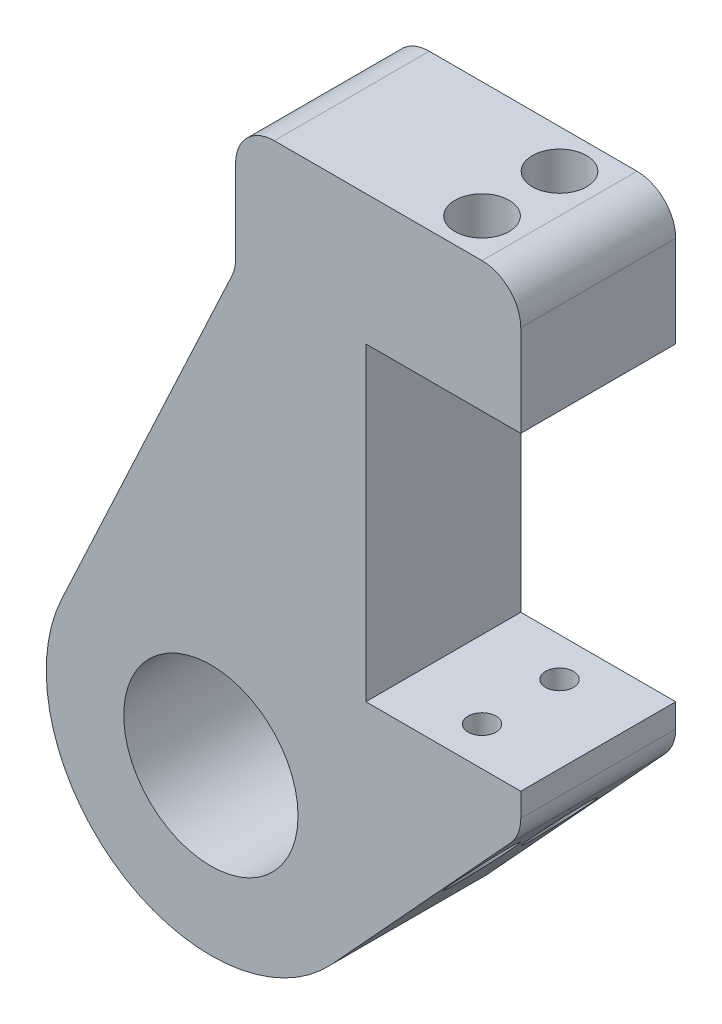
SolidWorks part; units mm, degrees
ref_plane "Front Plane" through (0, 0, 0) normal (0, 0, 1) x (1, 0, 0)
ref_plane "Top Plane" through (0, 0, 0) normal (0, 1, 0) x (1, 0, 0)
ref_plane "Right Plane" through (0, 0, 0) normal (1, 0, 0) x (0, 0, -1)
sketch "Sketch1" plane through (0, -13.0101, 793.75) normal (0, 0, 1) x (1, 0, 0)
  line L3 (-3.175, -125.9019) -> (-28.575, -125.9019)
  line L4 (-28.575, -75.1019) -> (-28.575, -125.9019)
  line L5 (-28.575, -75.1019) -> (-49.923, -75.1019) construction
  line L6 (-49.923, -75.1019) -> (-78.434, -136.2439)
  line L7 (-28.575, -75.1019) -> (-3.175, -75.1019)
  line L9 (-3.175, -75.1019) -> (-3.175, -53.7539)
  line L10 (-3.175, -53.7539) -> (-49.923, -53.7539)
  line L11 (-49.923, -75.1019) -> (-49.923, -53.7539)
  line L12 (-34.1032, -165.9096) -> (-3.175, -132.2519)
  line L13 (-3.175, -125.9019) -> (-3.175, -132.2519)
  circle A0 centre (-53.975, -147.6493) radius 14.2875
  arc A2 (-78.434, -136.2439) -> (-34.1032, -165.9096) centre (-53.975, -147.6493) ccw
  arc A4 (-39.9323, -145.0159) -> (-68.0177, -150.2826) centre (-53.975, -147.6493) ccw construction
  point P8 (-3.175, -145.7529)
  dimension "D1" = 12.7
  dimension "D2" = 65
  dimension "D3" = 21.348
  dimension "D4" = 6.35
extrude "Initial Plate" add sketch "Sketch1" along normal blind 25.4
sketch "Sketch3" plane through (0, -88.1119, 0) normal (0, -1, 0) x (1, 0, 0)
  line L0 (-15.875, 793.75) -> (-15.875, 800.1) construction
  line L1 (-28.575, 793.75) -> (-3.175, 793.75) construction
  circle A0 centre (-15.875, 800.1) radius 4.445
  circle A1 centre (-15.875, 800.1) radius 2.286
  dimension "D2" = 4.572
  dimension "D3" = 8.89
  dimension "D1" = 6.35
extrude "Initial Bolt Hole" cut sketch "Sketch3" against normal through all and the other way through all contours A1
extrude "Initial Head Hole" cut sketch "Sketch3<3>" against normal through all from offset 12.7 offset against normal yes
sketch "Sketch3<3>" plane through (0, -88.1119, 0) normal (0, -1, 0) x (1, 0, 0) same geometry as "Sketch3"
extrude "Other Head Hole" cut sketch "Sketch3<4>" against normal offset from surface (27.3077 mm away) 12.7 from vertex up to face at (-15.875, -138.9119, 797.814) starting at point (-34.1032, -178.9197, 793.75)
sketch "Sketch3<4>" plane through (0, -88.1119, 0) normal (0, -1, 0) x (1, 0, 0) same geometry as "Sketch3"
pattern_linear "Mounting Pattern" count 2 spacing 12.7 along (0, 0, 1) of "Initial Head Hole", "Initial Bolt Hole", "Other Head Hole"
fillet "Fillet1" radius 6.35 4 edges at (-3.175, -66.764, 806.45) (-49.923, -88.1119, 806.45) (-49.923, -66.764, 806.45) (-3.175, -145.2619, 806.45)
